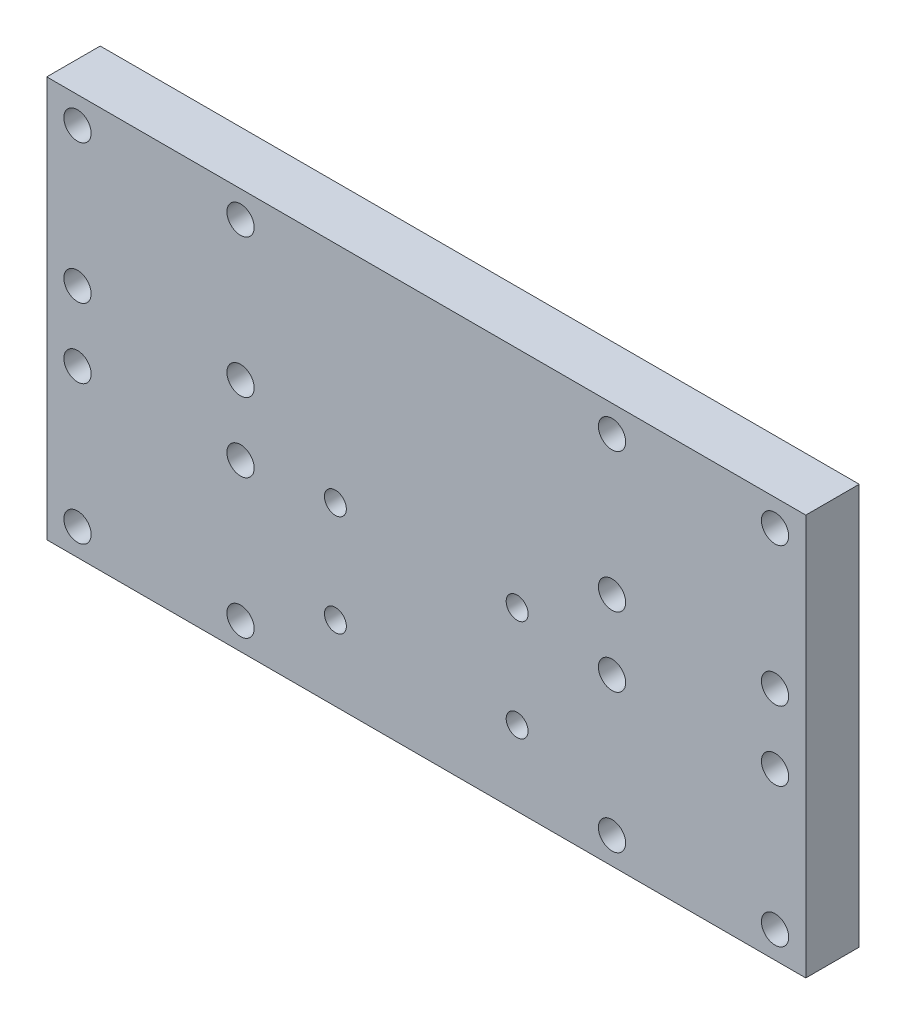
SolidWorks part; units mm, degrees
ref_plane "Front Plane" through (0, 0, 0) normal (0, 0, 1) x (1, 0, 0)
ref_plane "Top Plane" through (0, 0, 0) normal (0, 1, 0) x (1, 0, 0)
ref_plane "Right Plane" through (0, 0, 0) normal (1, 0, 0) x (0, 0, -1)
sketch "Sketch1" plane through (0, 0, 0) normal (0, 0, 1) x (1, 0, 0)
  line L1 (-71, -37.5) -> (71, -37.5)
  line L2 (-71, -37.5) -> (-71, 37.5)
  line L3 (-71, 37.5) -> (71, 37.5)
  line L4 (71, -37.5) -> (71, 37.5)
  line L5 (-71, -37.5) -> (71, 37.5) construction
  line L6 (-71, 37.5) -> (71, -37.5) construction
  point P0 (0, 0)
  dimension "D1" = 75
  dimension "D2" = 142
extrude "Boss-Extrude1" add sketch "Sketch1" along normal mid plane 10
sketch "Sketch2" plane through (0, 0, 5) normal (0, 0, 1) x (1, 0, 0)
  line L3 (-65.25, 37.5) -> (-65.25, -37.5)
  line L4 (-65.25, 37.5) -> (-65.25, -37.5) construction
  line L6 (65.25, -37.5) -> (65.25, 37.5)
  line L7 (65.25, -37.5) -> (65.25, 37.5) construction
  line L13 (-34.75, 37.5) -> (-34.75, -37.5)
  line L14 (-34.75, 37.5) -> (-34.75, -37.5) construction
  line L16 (34.75, -37.5) -> (34.75, 37.5)
  line L18 (34.75, -37.5) -> (34.75, 37.5) construction
  line L20 (71, 32.5) -> (-71, 32.5)
  line L21 (71, 32.5) -> (-71, 32.5) construction
  line L23 (-71, -32.5) -> (71, -32.5)
  line L24 (-71, -32.5) -> (71, -32.5) construction
  line L26 (71, 6.5) -> (-71, 6.5)
  line L27 (71, 6.5) -> (-71, 6.5) construction
  line L29 (-71, -6.5) -> (71, -6.5)
  line L30 (-71, -6.5) -> (71, -6.5) construction
  circle A0 centre (-65.25, 32.5) radius 2.55
  circle A1 centre (-34.75, 32.5) radius 2.55
  circle A2 centre (-34.75, 6.5) radius 2.55
  circle A3 centre (-65.25, 6.5) radius 2.55
  circle A4 centre (65.25, 32.5) radius 2.55
  circle A5 centre (65.25, 6.5) radius 2.55
  circle A6 centre (34.75, 6.5) radius 2.55
  circle A7 centre (34.75, 32.5) radius 2.55
  circle A8 centre (-65.25, -6.5) radius 2.55
  circle A9 centre (-34.75, -6.5) radius 2.55
  circle A10 centre (-34.75, -32.5) radius 2.55
  circle A11 centre (-65.25, -32.5) radius 2.55
  circle A12 centre (34.75, -6.5) radius 2.55
  circle A13 centre (65.25, -6.5) radius 2.55
  circle A14 centre (65.25, -32.5) radius 2.55
  circle A15 centre (34.75, -32.5) radius 2.55
  dimension "D9" = 5.1
  dimension "D10" = 5.1
  dimension "D11" = 5.1
  dimension "D12" = 5.1
  dimension "D13" = 5.1
  dimension "D14" = 5.1
  dimension "D15" = 5.1
  dimension "D16" = 5.1
  dimension "D17" = 5.1
  dimension "D18" = 5.1
  dimension "D19" = 5.1
  dimension "D20" = 5.1
  dimension "D21" = 5.1
  dimension "D22" = 5.1
  dimension "D23" = 5.1
  dimension "D24" = 5.1
  dimension "D1" = 5.75
  dimension "D2" = 5.75
  dimension "D3" = 36.25
  dimension "D4" = 36.25
  dimension "D5" = 5
  dimension "D6" = 5
  dimension "D7" = 31
  dimension "D8" = 31
extrude "Cut-Extrude1" cut sketch "Sketch2" against normal through all
sketch "Sketch3" plane through (0, 0, 5) normal (0, 0, 1) x (1, 0, 0)
  line L0 (-71, -37.5) -> (71, -37.5) construction
  line L1 (-17, -4.5) -> (17, -4.5) construction
  line L2 (-17, -4.5) -> (-17, -23.5) construction
  line L3 (-17, -23.5) -> (17, -23.5) construction
  line L4 (17, -4.5) -> (17, -23.5) construction
  line L5 (-17, -4.5) -> (17, -23.5) construction
  line L6 (-17, -23.5) -> (17, -4.5) construction
  line L7 (0, 37.5) -> (0, -37.5) construction
  line L8 (71, 37.5) -> (-71, 37.5) construction
  circle A0 centre (-17, -4.5) radius 2.05
  circle A1 centre (-17, -23.5) radius 2.05
  circle A2 centre (17, -23.5) radius 2.05
  circle A3 centre (17, -4.5) radius 2.05
  point P0 (0, 0)
  dimension "D3" = 4.1
  dimension "D4" = 4.1
  dimension "D5" = 4.1
  dimension "D6" = 4.1
  dimension "D1" = 34
  dimension "D2" = 19
  dimension "D7" = 14
  dimension "D8" = 17
extrude "Cut-Extrude2" cut sketch "Sketch3" against normal through all
equation "\"D4@Sketch3\"=\"D3@Sketch3\""
equation "\"D5@Sketch3\"=\"D3@Sketch3\""
equation "\"D6@Sketch3\"=\"D3@Sketch3\""
